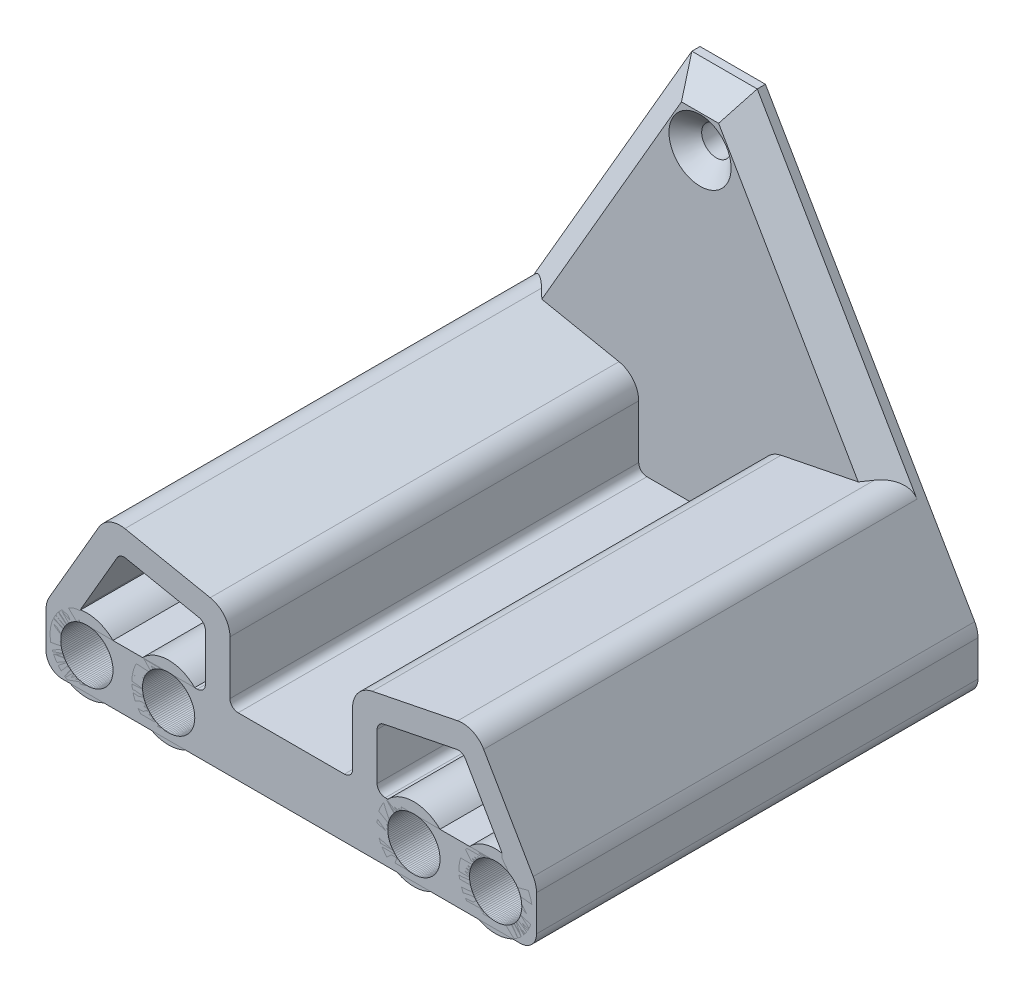
SolidWorks part; units mm, degrees
ref_plane "正面" through (0, 0, 0) normal (0, 0, 1) x (1, 0, 0)
ref_plane "平面" through (0, 0, 0) normal (0, 1, 0) x (1, 0, 0)
ref_plane "右側面" through (0, 0, 0) normal (1, 0, 0) x (0, 0, -1)
sketch "ｽｹｯﾁ1" plane through (0, 0, 0) normal (0, 0, 1) x (1, 0, 0)
  line L0 (-4, 48) -> (4, 48)
  line L3 (4, 48) -> (30, 3.1716)
  line L4 (30, 3.1716) -> (30, -4)
  line L5 (30, -4) -> (-30, -4)
  line L6 (-30, -4) -> (-30, 3.1716)
  line L7 (-30, 3.1716) -> (-4, 48)
  line L8 (0, 48) -> (0, 41) construction
  line L10 (-25, 0) -> (25, 0) construction
  line L11 (0, 41) -> (0, 0) construction
  line L12 (0, 0) -> (0, -4) construction
  circle A3 centre (0, 41) radius 1.8
  circle A4 centre (-25, 0) radius 1.8
  circle A5 centre (-15, 0) radius 1.8
  circle A6 centre (15, 0) radius 1.8
  circle A7 centre (25, 0) radius 1.8
  point P7 (0, 0)
  point P14 (0, -100.8688)
  point P15 (-15, -101.7852)
  point P16 (15, -103.4249)
  point P17 (0, -68.8518)
  point P18 (0, 0)
  dimension "D1" = 7
  dimension "D2" = 4
  dimension "D4" = 3.6
  dimension "D5" = 10
  dimension "D3" = 10
  dimension "D6" = 5
  dimension "D7" = 5
  dimension "D10" = 7.1716
  dimension "D8" = 50
  dimension "D9" = 52
  dimension "D11" = 7.1716
extrude "ﾎﾞｽ - 押し出し1" add sketch "ｽｹｯﾁ1" along normal blind 4
sketch "ｽｹｯﾁ2" plane through (0, 0, 4) normal (0, 0, 1) x (1, 0, 0)
  line L0 (-7.5, 3.1716) -> (-7.5, 13.1716)
  line L1 (-30, 3.1716) -> (30, 3.1716)
  line L2 (-30, 3.1716) -> (-30, -4)
  line L3 (-30, -4) -> (30, -4)
  line L4 (30, 3.1716) -> (30, -4)
  line L5 (-7.5, 13.1716) -> (-24.2001, 13.1716)
  line L6 (-4, 48) -> (-30, 3.1716) construction
  line L7 (-24.2001, 13.1716) -> (-30, 3.1716)
  line L8 (7.5, 3.1716) -> (7.5, 13.1716)
  line L9 (7.5, 13.1716) -> (24.2001, 13.1716)
  line L10 (30, 3.1716) -> (4, 48) construction
  line L11 (24.2001, 13.1716) -> (30, 3.1716)
  line L12 (-24.2001, 13.1716) -> (-30, 3.1716)
  line L13 (-7.5, 13.1716) -> (-22.4601, 16.1716)
  line L14 (-22.4601, 16.1716) -> (-24.2001, 13.1716)
  line L15 (7.5, 13.1716) -> (22.4601, 16.1716)
  line L16 (22.4601, 16.1716) -> (24.2001, 13.1716)
  circle A0 centre (-25, 0) radius 1.8
  circle A1 centre (-15, 0) radius 1.8
  circle A2 centre (15, 0) radius 1.8
  circle A3 centre (25, 0) radius 1.8
  circle A4 centre (-25, 0) radius 1.8 construction
  line M6 (-4, 48) -> (-30, 3.1716)
  line M7 (-30, 3.1716) -> (-30, -4)
  line M8 (-30, -4) -> (30, -4)
  line M9 (30, -4) -> (30, 3.1716)
  line M10 (30, 3.1716) -> (4, 48)
  circle M13 centre (-25, 0) radius 1.8
  circle M14 centre (-15, 0) radius 1.8
  circle M15 centre (15, 0) radius 1.8
  circle M16 centre (25, 0) radius 1.8
  dimension "D1" = 10
  dimension "D2" = 0
  dimension "D3" = 22.5
  dimension "D4" = 3
  dimension "D5" = 3
  dimension "D6" = 22.5
extrude "ﾎﾞｽ - 押し出し2" add sketch "ｽｹｯﾁ2" along normal blind 50 contours L0 L5 L1 M6 | L1 M7 M8 M9 M14 M16 M15 M13 | L5 L13 M6 | L15 L9 M10 | L9 L8 L1 M10 region at (-17.3715, 7.925, 4) region at (0, -0.4575, 4) region at (-18.0534, 14.1716, 4) region at (17.3715, 7.925, 4) region at (18.0534, 14.1716, 4)
fillet "ﾌｨﾚｯﾄ1" radius 3 2 edges at (7.5, 13.1716, 29) (-7.5, 13.1716, 29)
fillet "ﾌｨﾚｯﾄ2" radius 3 4 edges at (30, 3.1716, 27) (22.4601, 16.1716, 29) (-30, 3.1716, 27) (-22.4601, 16.1716, 29)
fillet "ﾌｨﾚｯﾄ3" radius 2 2 edges at (30, -4, 27) (-30, -4, 27)
fillet "ﾌｨﾚｯﾄ4" radius 1 2 edges at (7.5, 3.1716, 29) (-7.5, 3.1716, 29)
sketch "ｽｹｯﾁ4" plane through (0, 0, 54) normal (0, 0, 1) x (1, 0, 0)
  line L0 (-20.9431, 12.8076) -> (-10.5, 10.7134)
  line L1 (-10.5, 10.7134) -> (-10.5, 3.1716)
  line L2 (-10.5, 3.1716) -> (-26.5319, 3.1716)
  line L3 (-26.5319, 3.1716) -> (-20.9431, 12.8076)
  line L4 (0, 3.1716) -> (0, -4) construction
  line L5 (-6.5, 3.1716) -> (6.5, 3.1716) construction
  line L6 (-28, -4) -> (28, -4) construction
  line L7 (10.5, 3.1716) -> (26.5319, 3.1716)
  line L8 (10.5, 10.7134) -> (10.5, 3.1716)
  line L9 (20.9431, 12.8076) -> (10.5, 10.7134)
  line L10 (26.5319, 3.1716) -> (20.9431, 12.8076)
  line L11 (-9.9101, 13.6549) -> (-20.3533, 15.7491) construction
  line L12 (-7.5, 4.1716) -> (-7.5, 10.7134) construction
  line L13 (-23.5382, 14.3128) -> (-29.5951, 3.8697) construction
  dimension "D1" = 3
  dimension "D2" = 3
  dimension "D3" = 0
  dimension "D4" = 3
extrude "ｶｯﾄ - 押し出し1" cut sketch "ｽｹｯﾁ4" against normal blind 60
fillet "ﾌｨﾚｯﾄ5" radius 1 6 edges at (-10.5, 3.1716, 27) (-10.5, 10.7134, 27) (-20.9431, 12.8076, 27) (20.9431, 12.8076, 27) (10.5, 10.7134, 27) (10.5, 3.1716, 27)
sketch "ｽｹｯﾁ6" plane through (0, 0, 54) normal (0, 0, 1) x (1, 0, 0)
  line L4 (0, 3.1716) -> (0, -4) construction
  line L5 (-6.5, 3.1716) -> (6.5, 3.1716) construction
  line L6 (-28, -4) -> (28, -4) construction
  circle A2 centre (-25, 0) radius 4.5
  circle A3 centre (-25, 0) radius 1.8
  circle A4 centre (-15, 0) radius 1.8
  circle A5 centre (-15, 0) radius 4.5
  circle A6 centre (25, 0) radius 4.5
  circle A7 centre (25, 0) radius 1.8
  circle A8 centre (15, 0) radius 1.8
  circle A9 centre (15, 0) radius 4.5
  dimension "D1" = 3.6
  dimension "D2" = 9
extrude "ﾎﾞｽ - 押し出し3" add sketch "ｽｹｯﾁ6" against normal blind 54 separate body
fillet "ﾌｨﾚｯﾄ6" radius 1 2 edges at (-26.5319, 3.1716, 27) (26.5319, 3.1716, 27)
chamfer "面取り2" distance 2 angle 45 1 edges at (1.8, 41, 4)
sketch "ｽｹｯﾁ7" plane through (0, 0, 54) normal (0, 0, 1) x (1, 0, 0)
  line L0 (0, 3.1716) -> (0, -4) construction
  line L1 (-6.5, 3.1716) -> (6.5, 3.1716) construction
  line L2 (-28, -4) -> (28, -4) construction
  circle A0 centre (-25, 0) radius 3.2
  circle A1 centre (-15, 0) radius 3.2
  circle A2 centre (15, 0) radius 3.2
  circle A3 centre (25, 0) radius 3.2
  dimension "D1" = 6.4
extrude "ｶｯﾄ - 押し出し2" cut sketch "ｽｹｯﾁ7" against normal blind 40
chamfer "面取り3" distance 3 angle 45 3 edges at (13.7691, 31.1564, 4) (-13.7691, 31.1564, 4) (0, 48, 4)
